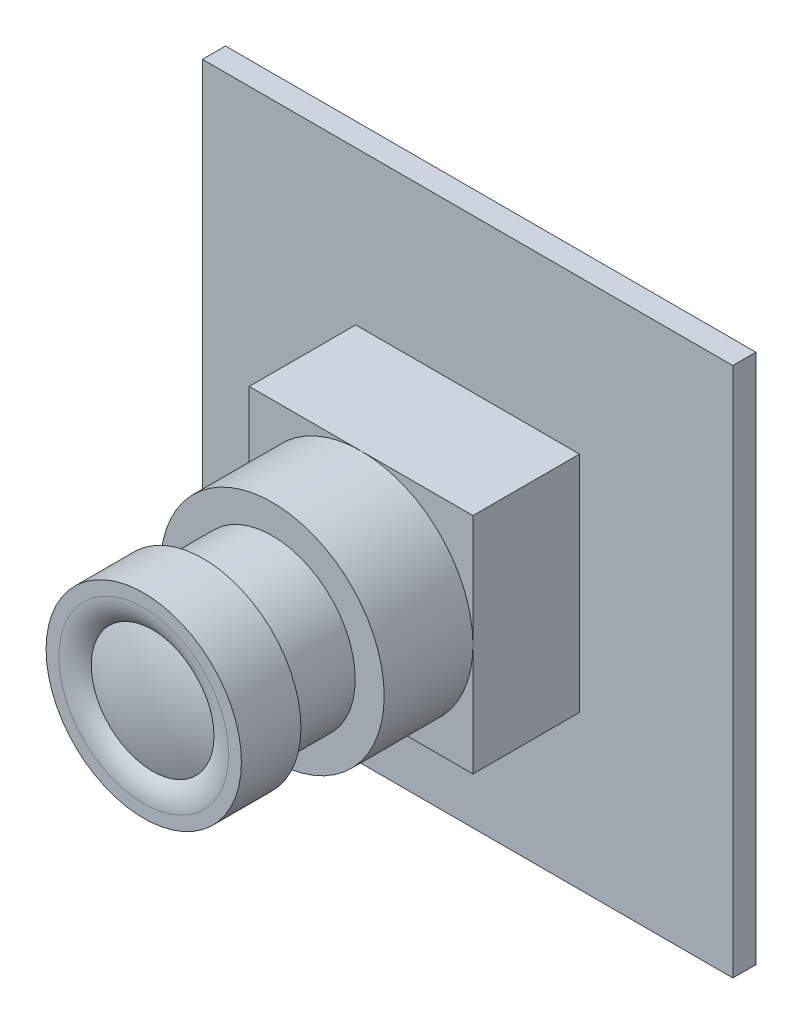
SolidWorks part; units mm, degrees
ref_plane "Front Plane" through (0, 0, 0) normal (0, 0, 1) x (1, 0, 0)
ref_plane "Top Plane" through (0, 0, 0) normal (0, 1, 0) x (1, 0, 0)
ref_plane "Right Plane" through (0, 0, 0) normal (1, 0, 0) x (0, 0, -1)
sketch "Sketch1" plane through (0, 0, 0) normal (0, 0, 1) x (1, 0, 0)
  line L1 (0, 37.9349) -> (37.9349, 37.9349)
  line L2 (0, 37.9349) -> (0, 0)
  line L3 (0, 0) -> (37.9349, 0)
  line L4 (37.9349, 37.9349) -> (37.9349, 0)
  dimension "D1" = 37.9349
extrude "Boss-Extrude1" add sketch "Sketch1" along normal blind 1.651
sketch "Sketch2" plane through (0, 0, 1.651) normal (0, 0, 1) x (1, 0, 0)
  line L0 (37.9349, 18.9675) -> (26.9685, 18.9675) construction
  line L1 (10.9665, 26.9685) -> (26.9684, 26.9685)
  line L2 (10.9665, 26.9685) -> (10.9665, 10.9665)
  line L3 (10.9665, 10.9665) -> (26.9685, 10.9665)
  line L4 (26.9684, 26.9685) -> (26.9685, 10.9665)
  line L5 (0, 0) -> (37.9349, 0) construction
  line L6 (37.9349, 0) -> (37.9349, 37.9349) construction
  line L7 (18.9674, 37.9349) -> (18.9675, 26.9685) construction
  line L10 (37.9349, 37.9349) -> (0, 37.9349) construction
  dimension "D1" = 16.002
extrude "Boss-Extrude2" add sketch "Sketch2" along normal blind 7.62
sketch "Sketch3" plane through (0, 0, 9.271) normal (0, 0, 1) x (1, 0, 0)
  line L1 (26.9684, 26.9685) -> (10.9665, 26.9685) construction
  line L2 (26.9685, 10.9665) -> (26.9684, 26.9685) construction
  line L3 (10.9665, 26.9685) -> (10.9665, 10.9665) construction
  line L4 (10.9665, 10.9665) -> (26.9685, 10.9665) construction
  circle A0 centre (18.9675, 18.9675) radius 8.001
extrude "Boss-Extrude3" add sketch "Sketch3" along normal blind 6.35
sketch "Sketch4" plane through (0, 0, 15.621) normal (0, 0, 1) x (1, 0, 0)
  circle A0 centre (18.9675, 18.9675) radius 5.9309
  circle A1 centre (18.9675, 18.9675) radius 8.001 construction
  dimension "D1" = 11.8618
extrude "Boss-Extrude4" add sketch "Sketch4" along normal blind 4.9403
sketch "Sketch5" plane through (0, 0, 20.5613) normal (0, 0, 1) x (1, 0, 0)
  circle A0 centre (18.9675, 18.9675) radius 6.985
  circle A1 centre (18.9675, 18.9675) radius 5.9309 construction
  dimension "D1" = 13.97
extrude "Boss-Extrude5" add sketch "Sketch5" along normal blind 4.2545
sketch "Sketch6" plane through (0, 0, 24.8158) normal (0, 0, 1) x (1, 0, 0)
  circle A0 centre (18.9675, 18.9675) radius 4.3878
  circle A1 centre (18.9675, 18.9675) radius 6.985 construction
  dimension "D1" = 8.7757
extrude "Cut-Extrude1" cut sketch "Sketch6" against normal blind 0.635
fillet "Fillet2" radius 2.54 1 edges at (23.3553, 18.9675, 24.8158)
dome "Dome1" faces to dome 1 distance 0.762 reverse direction no elliptical dome no face at (23.3553, 18.9675, 24.1808) parameters "D1"=0.762
sketch "Sketch9" plane through (0, 0, 1.651) normal (0, 0, 1) x (1, 0, 0)
  line L0 (32.8168, 32.8168) -> (37.9349, 32.8168) construction
  line L1 (0, 0) -> (37.9349, 0) construction
  line L2 (37.9349, 0) -> (37.9349, 37.9349) construction
  line L3 (32.8168, 37.9349) -> (32.8168, 32.8168) construction
  line L4 (0, 37.9349) -> (0, 0) construction
  line L5 (37.9349, 37.9349) -> (0, 37.9349) construction
  line L6 (5.1181, 37.9349) -> (5.1181, 32.8168) construction
  line L7 (0, 32.8168) -> (5.1181, 32.8168) construction
  line L8 (5.1181, 0) -> (5.1181, 5.1181) construction
  line L9 (0, 5.1181) -> (5.1181, 5.1181) construction
  line L10 (37.9349, 5.1181) -> (32.8168, 5.1181) construction
  line L11 (32.8168, 0) -> (32.8168, 5.1181) construction
  line L12 (18.9674, 37.9349) -> (18.9674, 36.1569) construction
  line L13 (15.508, 36.1569) -> (22.4269, 36.1569)
  line L14 (22.4269, 35.0692) -> (23.5146, 35.0692) construction
  line L15 (15.508, 33.9815) -> (22.4269, 33.9815)
  line L16 (15.508, 35.0692) -> (22.4269, 35.0692) construction
  line L17 (18.9674, 33.9815) -> (18.9675, 26.9685) construction
  line L18 (26.9684, 26.9685) -> (10.9665, 26.9685) construction
  line L19 (14.4203, 35.0692) -> (15.508, 35.0692) construction
  line L20 (15.375, 3.9534) -> (22.5599, 3.9534)
  line L21 (22.4269, 2.8739) -> (23.5146, 2.8739) construction
  line L22 (15.375, 1.7943) -> (22.5599, 1.7943)
  line L23 (15.508, 2.8739) -> (22.4269, 2.8739) construction
  line L24 (14.4203, 2.8739) -> (15.508, 2.8739) construction
  line L25 (33.9815, 22.5599) -> (33.9815, 15.375)
  line L26 (18.9675, 10.9665) -> (18.9675, 3.9534) construction
  line L27 (18.9675, 3.9534) -> (18.9674, 1.7943) construction
  line L28 (36.1394, 22.5599) -> (36.1394, 15.375)
  line L29 (10.9665, 10.9665) -> (26.9685, 10.9665) construction
  line L30 (18.9674, 1.7943) -> (18.9674, 0) construction
  line L31 (18.9674, 36.1569) -> (18.9674, 33.9815) construction
  line L32 (33.9815, 15.375) -> (36.1394, 15.375) construction
  line L33 (35.0604, 22.4269) -> (35.0604, 15.508) construction
  line L34 (35.0604, 23.5141) -> (35.0604, 22.4269) construction
  line L35 (35.0604, 15.508) -> (35.0604, 14.4209) construction
  line L36 (26.9685, 18.9675) -> (33.9815, 18.9675) construction
  line L37 (26.9685, 10.9665) -> (26.9684, 26.9685) construction
  line L38 (1.7955, 22.5599) -> (1.7955, 15.375)
  line L39 (3.9534, 22.5599) -> (3.9534, 15.375)
  line L40 (1.7955, 15.375) -> (3.9534, 15.375) construction
  line L41 (2.8745, 22.4269) -> (2.8745, 15.508) construction
  line L42 (2.8745, 23.5141) -> (2.8745, 22.4269) construction
  line L43 (2.8745, 15.508) -> (2.8745, 14.4209) construction
  line L44 (3.9534, 18.9675) -> (10.9665, 18.9675) construction
  line L45 (10.9665, 26.9685) -> (10.9665, 10.9665) construction
  line L46 (1.7955, 22.5599) -> (3.9534, 22.5599) construction
  line L47 (0, 18.9675) -> (1.7955, 18.9675) construction
  circle A0 centre (32.8168, 32.8168) radius 1.1176
  circle A1 centre (5.1181, 32.8168) radius 1.1176
  circle A2 centre (5.1181, 5.1181) radius 1.1176
  circle A3 centre (32.8168, 5.1181) radius 1.1176
  arc A4 (22.4269, 36.1569) -> (22.4269, 33.9815) centre (22.4269, 35.0692) cw
  arc A5 (15.508, 36.1569) -> (15.508, 33.9815) centre (15.508, 35.0692) ccw
  arc A6 (22.5599, 3.9534) -> (22.5599, 1.7943) centre (22.4269, 2.8739) cw
  arc A7 (15.375, 3.9534) -> (15.375, 1.7943) centre (15.508, 2.8739) ccw
  arc A8 (33.9815, 22.5599) -> (36.1394, 22.5599) centre (35.0604, 22.4269) cw
  arc A9 (33.9815, 15.375) -> (36.1394, 15.375) centre (35.0604, 15.508) ccw
  arc A10 (1.7955, 22.5599) -> (3.9534, 22.5599) centre (2.8745, 22.4269) cw
  arc A11 (1.7955, 15.375) -> (3.9534, 15.375) centre (2.8745, 15.508) ccw
  dimension "D1" = 2.2352
  dimension "D3" = 1.0877
  dimension "D2" = 5.1181
  dimension "D4" = 1.778
  dimension "D5" = 7.013
  dimension "D6" = 6.919
  dimension "D7" = 1.0877
  dimension "D8" = 6.919
  dimension "D9" = 7.013
  dimension "D10" = 2.1591
  dimension "D11" = 1.7943
  dimension "D12" = 6.919
  dimension "D13" = 1.0871
  dimension "D14" = 7.013
  dimension "D15" = 6.919
  dimension "D16" = 1.0871
  dimension "D17" = 7.013
  dimension "D18" = 1.7955
